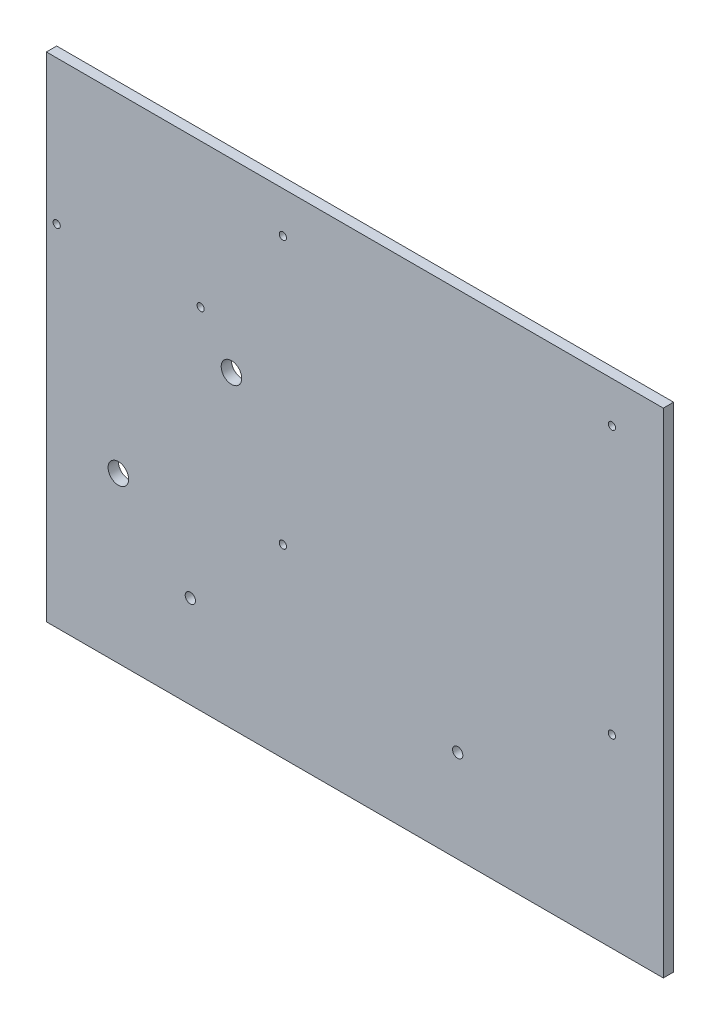
SolidWorks part; units mm, degrees
material "Acrylic (Medium-high impact)"
ref_plane "Front Plane" through (0, 0, 0) normal (0, 0, 1) x (1, 0, 0)
ref_plane "Top Plane" through (0, 0, 0) normal (0, 1, 0) x (1, 0, 0)
ref_plane "Right Plane" through (0, 0, 0) normal (1, 0, 0) x (0, 0, -1)
sketch "Sketch1" plane through (0, 0, 0) normal (0, 0, 1) x (1, 0, 0)
  line L1 (0, 0) -> (381, 0)
  line L2 (0, 0) -> (0, 304.8)
  line L3 (0, 304.8) -> (381, 304.8)
  line L4 (381, 0) -> (381, 304.8)
  dimension "D1" = 381
  dimension "D2" = 304.8
extrude "Boss-Extrude1" add sketch "Sketch1" along normal blind 6.35
sketch "Sketch2" plane through (0, 0, 6.35) normal (0, 0, 1) x (1, 0, 0)
  line L0 (381, 304.8) -> (0, 304.8) construction
  line L1 (0, 304.8) -> (0, 0) construction
  circle A0 centre (6.35, 215.9) radius 2.2225
  circle A1 centre (95.25, 215.9) radius 2.2225
  dimension "D1" = 4.445
  dimension "D2" = 88.9
  dimension "D3" = 88.9
  dimension "D4" = 6.35
extrude "Cut-Extrude1" cut sketch "Sketch2" against normal through all
sketch "Sketch3" plane through (0, 0, 6.35) normal (0, 0, 1) x (1, 0, 0)
  line L1 (0, 0) -> (381, 0) construction
  line L2 (0, 304.8) -> (0, 0) construction
  circle A0 centre (88.9, 57.15) radius 3.175
  circle A1 centre (254, 57.15) radius 3.175
  point P9 (190.5, 0)
  dimension "D2" = 6.35
  dimension "D1" = 165.1
  dimension "D3" = 88.9
  dimension "D4" = 57.15
extrude "Cut-Extrude2" cut sketch "Sketch3" against normal through all
hole_wizard "#8 Clearance Hole1" positions "Sketch4" profile "Sketch5" hole size "#8" standard "ANSI Inch" end condition through all
sketch "Sketch4" plane through (0, 0, 6.35) normal (0, 0, 1) x (1, 0, 0)
  line L1 (381, 0) -> (381, 304.8) construction
  circle A1 centre (254, 57.15) radius 3.175 construction
  point P0 (146.05, 114.3)
  point P2 (349.25, 114.3)
  point P15 (146.05, 279.4)
  point P17 (349.25, 279.4)
  point P20 (0, 0)
  point P21 (0, 0)
  point P22 (0, 0)
  dimension "D1" = 203.2
  dimension "D2" = 31.75
  dimension "D3" = 57.15
  dimension "D4" = 165.1
sketch "Sketch5" plane through (146.05, 114.3, 6.35) normal (1, 0, 0) x (0, -1, 0)
  line L0 (0, 0) -> (0, 6.35)
  line L1 (0, 6.35) -> (2.2479, 6.35)
  line L2 (2.2479, 6.35) -> (2.2479, 0)
  line L5 (2.2479, 0) -> (0, 0)
  line L11 (0, -6.35) -> (0, 107.95) construction
  dimension "Thru Hole Dia." = 4.4958
  dimension "Thru Hole Depth" = 6.35
sketch "Sketch6" plane through (0, 0, 6.35) normal (0, 0, 1) x (1, 0, 0)
  line L1 (0, 0) -> (381, 0) construction
  circle A0 centre (114.3, 190.5) radius 6.35
  circle A2 centre (95.25, 215.9) radius 2.2225 construction
  dimension "D1" = 184.15
  dimension "D2" = 12.7
  dimension "D3" = 12.7
extrude "Cut-Extrude3" cut sketch "Sketch6" against normal through all
sketch "Sketch7" plane through (0, 0, 6.35) normal (0, 0, 1) x (1, 0, 0)
  line L0 (0, 304.8) -> (0, 0) construction
  circle A0 centre (44.45, 101.6) radius 6.35
  circle A1 centre (88.9, 57.15) radius 3.175 construction
  dimension "D1" = 12.7
  dimension "D2" = 38.1
  dimension "D3" = 44.45
extrude "Cut-Extrude4" cut sketch "Sketch7" against normal through all
